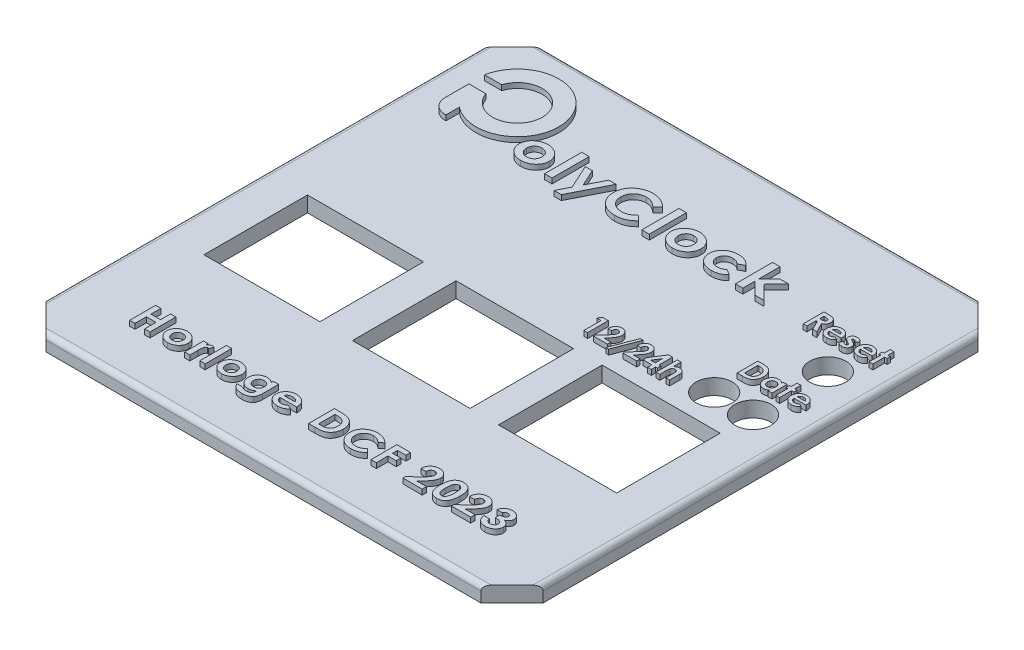
SolidWorks part; units mm, degrees
ref_plane "Plan de face" through (0, 0, 0) normal (0, 0, 1) x (1, 0, 0)
ref_plane "Plan de dessus" through (0, 0, 0) normal (0, 1, 0) x (1, 0, 0)
ref_plane "Plan de droite" through (0, 0, 0) normal (1, 0, 0) x (0, 0, -1)
sketch "Esquisse1" plane through (0, 0, 0) normal (0, 1, 0) x (1, 0, 0)
  line L1 (0, 0) -> (96, 0)
  line L2 (0, 0) -> (0, 96)
  line L3 (0, 96) -> (96, 96)
  line L4 (96, 0) -> (96, 96)
  dimension "D1" = 96
  dimension "D2" = 96
extrude "Boss.-Extru.1" add sketch "Esquisse1" along normal blind 3 contours L2 L1 L4 L3
sketch "Esquisse2" plane through (0, 3, 0) normal (0, 1, 0) x (1, 0, 0)
  line L0 (48, 96) -> (48, 0) construction
  line L1 (0, 96) -> (96, 96) construction
  line L2 (0, 0) -> (96, 0) construction
  line L3 (0, 48) -> (96, 48) construction
  line L4 (0, 0) -> (0, 96) construction
  line L5 (96, 0) -> (96, 96) construction
  line L6 (96, 96) -> (96, 93) construction
  line L7 (96, 96) -> (93, 96) construction
  line L8 (88.4521, 97.5479) -> (97.5479, 88.4521) construction
  line L9 (90, 96) -> (96, 96)
  line L10 (96, 96) -> (96, 90)
  line L11 (96, 90) -> (90, 96)
  line L12 (96, 0) -> (96, 6)
  line L13 (90, 0) -> (96, 0)
  line L14 (96, 6) -> (90, 0)
  line L15 (90, 0) -> (96, 6)
  line L16 (96, 6) -> (96, 0)
  line L17 (96, 0) -> (90, 0)
  line L18 (0, 6) -> (6, 0)
  line L19 (6, 0) -> (0, 0)
  line L20 (0, 0) -> (0, 6)
  line L21 (6, 96) -> (0, 90)
  line L22 (0, 90) -> (0, 96)
  line L23 (0, 96) -> (6, 96)
  point P15 (94.5, 96)
  point P17 (93, 93)
  point P21 (96, 90)
  point P22 (93, 93)
  point P23 (90, 96)
  point P28 (48, 48)
  point P41 (48, 48)
  line M11 (96, 96) -> (0, 96)
  line M12 (0, 96) -> (0, 0)
  line M13 (0, 0) -> (96, 0)
  line M14 (96, 0) -> (96, 96)
  dimension "D1" = 3
  dimension "D2" = 3
  dimension "D3" = 45
  dimension "D4" = 4
extrude "Enlèv. mat.-Extru.1" cut sketch "Esquisse2" against normal up to next contours L11 M14 M11 | L18 M12 M13 | L14 M14 M13 | L23 L21 L22 region at (94, 3, -94) region at (94, 3, -2) region at (2, 3, -2)
fillet "Congé1" radius 1 4 edges at (96, 3, -48) (48, 3, -96) (0, 3, -48) (48, 3, 0)
sketch "Esquisse3" plane through (0, 0, 0) normal (0, -1, 0) x (1, 0, 0)
  line L0 (48, 0) -> (48, -102.5134) construction
  line L1 (6, 0) -> (90, 0) construction
  line L2 (0, -10) -> (14, -10) construction
  line L3 (0, -6) -> (0, -90) construction
  line L4 (14, -10) -> (14, 0) construction
  circle A0 centre (14, -10) radius 2.5
  circle A1 centre (82, -10) radius 2.5
  dimension "D1" = 14
  dimension "D2" = 10
extrude "Enlèv. mat.-Extru.2" cut sketch "Esquisse3" against normal blind 2
sketch "Esquisse4" plane through (0, 3, 0) normal (0, 1, 0) x (1, 0, 0)
  line L0 (8.5, 36.2885) -> (8.5, 7.5765) construction
  line L1 (0, 6) -> (0, 90) construction
  line L2 (5.0579, 29) -> (84.016, 29) construction
  line L3 (90, 0) -> (6, 0) construction
  line L4 (29.9, 46.3629) -> (29.9, 7.5765) construction
  line L5 (58.9, 48.8815) -> (58.9, 9.4654) construction
  line L6 (65.4, 58.8929) -> (65.4, 19.4768) construction
  line L7 (87.2, 58.8929) -> (87.2, 10.9969) construction
  line L8 (37.2, 60.8449) -> (37.2, 7.5765) construction
  line L9 (96, 90) -> (96, 6) construction
  line L10 (10.5278, 48) -> (90.8922, 48) construction
  line L12 (64.9, 48.5) -> (87.7, 48.5)
  line L13 (64.9, 48.5) -> (64.9, 28.5)
  line L14 (64.9, 28.5) -> (87.7, 28.5)
  line L15 (87.7, 48.5) -> (87.7, 28.5)
  line L16 (36.7, 48.5) -> (59.4, 48.5)
  line L17 (36.7, 48.5) -> (36.7, 28.5)
  line L18 (36.7, 28.5) -> (59.4, 28.5)
  line L19 (59.4, 48.5) -> (59.4, 28.5)
  line L20 (8, 48.5) -> (30.4, 48.5)
  line L21 (8, 48.5) -> (8, 28.5)
  line L22 (8, 28.5) -> (30.4, 28.5)
  line L23 (30.4, 48.5) -> (30.4, 28.5)
  dimension "D1" = 8.5
  dimension "D2" = 29
  dimension "D3" = 21.4
  dimension "D4" = 37.2
  dimension "D5" = 21.7
  dimension "D6" = 65.4
  dimension "D7" = 21.8
  dimension "D8" = 8.8
  dimension "D9" = 19
  dimension "D10" = 0.5
  dimension "D11" = 0.5
  dimension "D12" = 0.5
  dimension "D13" = 0.5
  dimension "D14" = 0.5
  dimension "D15" = 0.5
  dimension "D16" = 0.5
  dimension "D17" = 0.5
  dimension "D18" = 0.5
  dimension "D19" = 0.5
  dimension "D20" = 0.5
  dimension "D21" = 0.5
extrude "Enlèv. mat.-Extru.3" cut sketch "Esquisse4" against normal up to next
sketch "Esquisse5" plane through (0, 3, 0) normal (0, 1, 0) x (1, 0, 0)
  line L0 (77.3, 73.3709) -> (77.3, 51.75) construction
  line L1 (96, 90) -> (96, 6) construction
  line L2 (84.8, 75.075) -> (84.8, 53.2891) construction
  line L3 (72.6823, 51.75) -> (90.8, 51.75) construction
  line L4 (90, 0) -> (6, 0) construction
  line L5 (69.7859, 66.2) -> (93.3348, 66.2) construction
  line L6 (75.2009, 57.75) -> (93.3348, 57.75) construction
  line L7 (71.8008, 72.2) -> (93.3348, 72.2) construction
  line L8 (83.3, 59.2078) -> (83.3, 44.5999) construction
  line L9 (90.8, 75.075) -> (90.8, 45.9851) construction
  circle A3 centre (87.8, 69.2) radius 3.5
  circle A4 centre (80.3, 54.75) radius 3.5
  circle A5 centre (87.8, 54.75) radius 3.5
  point P27 (87.8, 69.2)
  point P28 (80.3, 54.75)
  point P29 (87.8, 54.75)
  dimension "D9" = 7
  dimension "D10" = 7
  dimension "D11" = 7
  dimension "D1" = 18.7
  dimension "D2" = 11.2
  dimension "D3" = 51.75
  dimension "D4" = 66.2
  dimension "D5" = 6
  dimension "D6" = 6
  dimension "D7" = 6
  dimension "D8" = 6
extrude "Enlèv. mat.-Extru.4" cut sketch "Esquisse5" against normal up to next
sketch "Esquisse8" plane through (0, 3, 0) normal (0, 1, 0) x (1, 0, 0)
  line L0 (6.0055, 84.6976) -> (9.3075, 84.6976)
  line L1 (6.0055, 81.6655) -> (9.3075, 81.6655)
  line L2 (8.9764, 74.276) -> (8.9764, 76.841)
  line L3 (6.0055, 76.841) -> (6.0055, 81.6655)
  line L4 (8.9764, 74.276) -> (90.6649, 74.276) construction
  circle A0 centre (13.8703, 83.1816) radius 8.0095
  circle A1 centre (13.8703, 83.1816) radius 4.8081
  arc A2 (6.0055, 76.841) -> (8.9764, 74.276) centre (8.7735, 77.0439) ccw
  text T0 "    <b>olyClock</b>" font "Century Gothic" height 7
extrude "Boss.-Extru.2" add sketch "Esquisse8" along normal blind 1 contours A1 L1 A0 L0 | L3 A2 L2 A0 region at (14.6103, 3, -90.9303) region at (7.3315, 3, -76.8736)
sketch "Esquisse9" plane through (0, 3, 0) normal (0, 1, 0) x (1, 0, 0)
  line L0 (20.4341, 73.9529) -> (80.4147, 73.9529) construction
  text T1 "<b>olyClock</b>" font "Century Gothic" height 7
extrude "Boss.-Extru.3" add sketch "Esquisse9" along normal blind 1
sketch "Esquisse12" plane through (0, 3, 0) normal (0, 1, 0) x (1, 0, 0)
  line L0 (40.822, 51.526) -> (75.3268, 51.526) construction
  line L1 (76.3343, 73.8157) -> (92.5792, 73.8157) construction
  line L2 (61.0967, 59.2078) -> (92.5792, 59.2078) construction
  text T0 "<b>Reset</b>" font "Century Gothic" height 4
  text T1 "<b>Date</b>" font "Century Gothic" height 4
  text T2 "<b>12/24h</b>" font "Century Gothic" height 4
  point P6 (61.0967, 59.3337)
  point P7 (93.9645, 59.3337)
  point P8 (92.5792, 73.8157)
  point P9 (92.5792, 59.2078)
extrude "Boss.-Extru.4" add sketch "Esquisse12" along normal blind 1
sketch "Esquisse13" plane through (0, 3, 0) normal (0, 1, 0) x (1, 0, 0)
  line L0 (3.72, 9.3774) -> (92.2841, 9.3774) construction
  line L1 (48, 95) -> (48, 1) construction
  line L2 (91, 95) -> (5, 95) construction
  line L3 (5, 1) -> (91, 1) construction
  text T0 "<b>Horloge DCF 2023</b>" font "Century Gothic" height 5
extrude "Boss.-Extru.5" add sketch "Esquisse13" along normal blind 1
